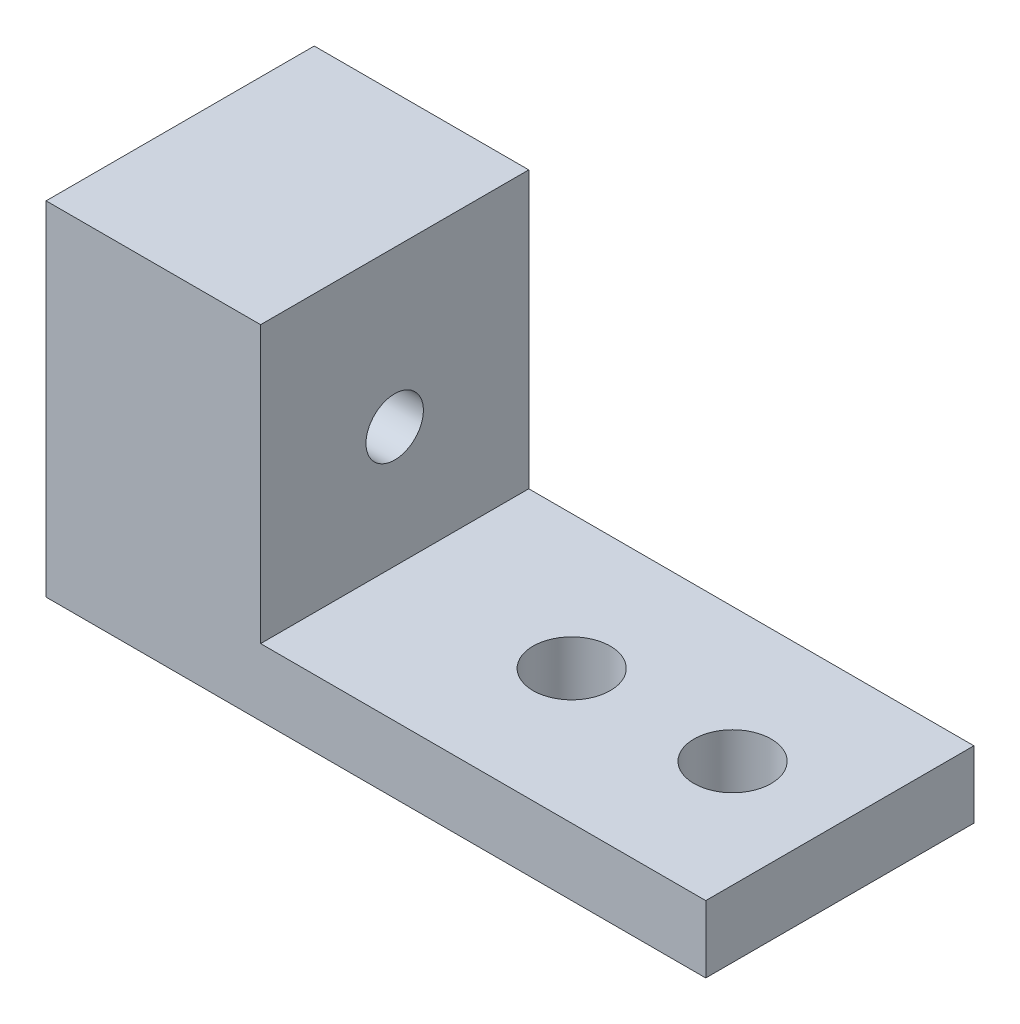
SolidWorks part; units mm, degrees
material "Plain Carbon Steel"
ref_plane "Front Plane" through (0, 0, 0) normal (0, 0, 1) x (1, 0, 0)
ref_plane "Top Plane" through (0, 0, 0) normal (0, 1, 0) x (1, 0, 0)
ref_plane "Right Plane" through (0, 0, 0) normal (1, 0, 0) x (0, 0, -1)
sketch "Sketch1" plane through (0, 0, 0) normal (0, 0, 1) x (1, 0, 0)
  line L0 (0, 0) -> (0, 16.256)
  line L1 (0, 16.256) -> (10.16, 16.256)
  line L2 (10.16, 16.256) -> (10.16, 3.175)
  line L3 (10.16, 3.175) -> (31.242, 3.175)
  line L4 (31.242, 3.175) -> (31.242, 0)
  line L5 (31.242, 0) -> (0, 0)
  dimension "D1" = 10.16
  dimension "D2" = 3.175
  dimension "D4" = 16.256
  dimension "D3" = 21.082
extrude "Boss-Extrude1" add sketch "Sketch1" against normal mid plane 12.7
sketch "Sketch2" plane through (0, 0, 0) normal (-1, 0, 0) x (0, 0, 1)
  circle A0 centre (0, 8.89) radius 1.3589
  dimension "D1" = 2.7178
  dimension "D2" = 8.89
extrude "Cut-Extrude1" cut sketch "Sketch2" against normal up to next
sketch "Sketch3" plane through (0, 0, 0) normal (0, -1, 0) x (1, 0, 0)
  circle A0 centre (18.542, 0) radius 1.8288
  dimension "D1" = 3.6576
  dimension "D2" = 8.382
extrude "Cut-Extrude2" cut sketch "Sketch3" against normal up to next
pattern_linear "LPattern1" count 2 spacing 7.62 along (1, 0, 0) of "Cut-Extrude2"
equation "\"D2@Sketch1\"=1/8"
equation "\"Middle Coupler Inner Daimeter\"= 3.875in"
equation "\"Middle Coupler  Wall Thickness\" = 0.25in"
equation "\"Middle Coupler Bottom Thickness\"= 0.2in"
equation "\"Bearing Rail Offset\"= 0.45in"
equation "\"3-56 UNF Tap\"= 0.089in"
equation "\"3-48 Tap\"= 0.079in"
equation "\"3-56 UNF Clearance\"= 0.104in"
equation "\"3-48 Clearance\" = 0.104in"
equation "\"Ball Bearing Distance\"= 0.03in"
equation "\"TCA Outer Diameter\" = 6in"
equation "\"Interstage Aeroframe Wall Thickness\" = 0.072in"
equation "\"Compression Spring OD\"= 0.42in"
equation "\"10-24 Tap\"= 0.157in"
equation "\"10-24 Clearance\"= 0.196in"
equation "\"Lower Stage Fuselage Wall Thickness\" = 0.25in"
equation "\"6-32 Tap\" = 0.107in"
equation "\"6-32 Clearance\" = 0.144"
equation "\"1/4-20 Tap\" = 0.201in"
equation "\"12-24 Tap\" = 0.177in"
equation "\"12-24 Major Diameter\"= 0.216in"
equation "\"D1@Sketch2\"=\"6-32 Tap\""
equation "\"D1@Sketch3\"=\"6-32 Clearance\""
